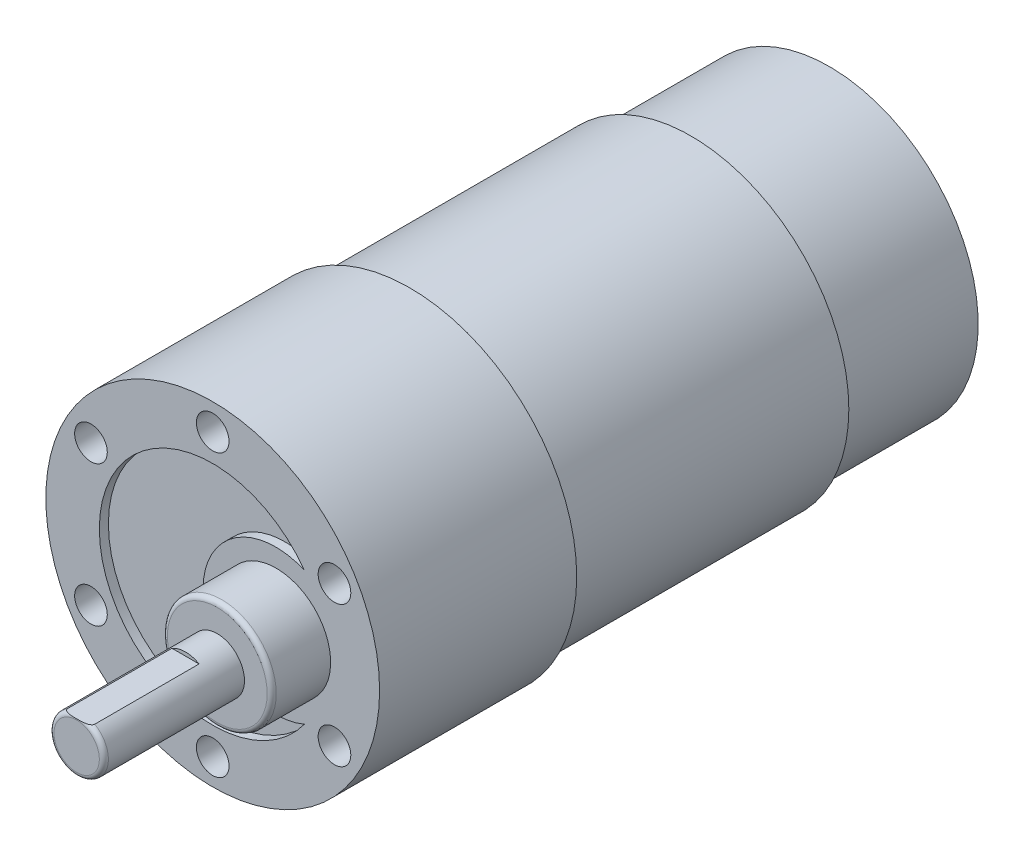
SolidWorks part; units mm, degrees
ref_plane "Front Plane" through (0, 0, 0) normal (0, 0, 1) x (1, 0, 0)
ref_plane "Top Plane" through (0, 0, 0) normal (0, 1, 0) x (1, 0, 0)
ref_plane "Right Plane" through (0, 0, 0) normal (1, 0, 0) x (0, 0, -1)
sketch "Sketch1" plane through (0, 0, 0) normal (0, 0, 1) x (1, 0, 0)
  circle A0 centre (0, 0) radius 18.4
  dimension "D1" = 36.8
extrude "Boss-Extrude1" add sketch "Sketch1" along normal blind 21.73
sketch "Sketch2" plane through (0, 0, 0) normal (0, 0, -1) x (-1, 0, 0)
  circle A0 centre (0, 0) radius 17.4
  dimension "D1" = 34.8
extrude "Boss-Extrude2" add sketch "Sketch2" along normal blind 31
sketch "Sketch3" plane through (0, 0, 21.73) normal (0, 0, 1) x (1, 0, 0)
  circle A0 centre (7, 0) radius 6
  dimension "D1" = 12
  dimension "D2" = 7
extrude "Boss-Extrude3" add sketch "Sketch3" along normal blind 6.5
fillet "Fillet1" radius 0.5 1 edges at (13, 0, 28.23)
sketch "Sketch4" plane through (0, 0, 28.23) normal (0, 0, 1) x (1, 0, 0)
  line L0 (7, -6.8172) -> (7, 7.1125) construction
  circle A0 centre (7, 0) radius 3
  dimension "D1" = 6
extrude "Boss-Extrude4" add sketch "Sketch4" along normal blind 15.5
sketch "Sketch5" plane through (0, 0, 43.73) normal (0, 0, 1) x (1, 0, 0)
  line L0 (5.5033, 2.6) -> (8.4967, 2.6)
  line L1 (7, -3) -> (9.3109, -3) construction
  circle A0 centre (7, 0) radius 3 construction
  circle A1 centre (7, 0) radius 3 construction
  arc A2 (8.4967, 2.6) -> (5.5033, 2.6) centre (7, 0) ccw
  dimension "D1" = 5.6
extrude "Cut-Extrude1" cut sketch "Sketch5" against normal blind 12
sketch "Sketch8" plane through (0, 0, 21.73) normal (0, 0, 1) x (1, 0, 0)
  line L0 (-0.5907, 0) -> (14.4711, 0) construction
  line L1 (7, 7.3586) -> (7, -7.457) construction
  arc A0 (10.1162, 7.3426) -> (10.1162, -7.3426) centre (0, 0) ccw
  arc A1 (10.1162, 7.3426) -> (10.1162, -7.3426) centre (6.9402, 0) ccw
  dimension "D1" = 25
  dimension "D2" = 16
extrude "Cut-Extrude2" cut sketch "Sketch8" against normal blind 1
sketch "Sketch9" plane through (0, 0, -31) normal (0, 0, -1) x (-1, 0, 0)
  circle A0 centre (0, 0) radius 4
  dimension "D1" = 8
extrude "Boss-Extrude5" add sketch "Sketch9" along normal blind 1
fillet "Fillet2" radius 0.5 1 edges at (-4, 0, -32)
ref_plane "Plane1" through (0, 0, -34) normal (0, 0, -1) x (-1, 0, 0)
sketch "Sketch10" plane through (0, 0, -34) normal (0, 0, -1) x (-1, 0, 0)
  circle A0 centre (0, 0) radius 14
  dimension "D1" = 28
extrude "Boss-Extrude6" add sketch "Sketch10" along normal blind 1.5 separate body
sketch "Sketch11" plane through (0, 0, -31) normal (0, 0, -1) x (-1, 0, 0)
  line L0 (0, 11.55) -> (0, 12.55) construction
  line L1 (-1.75, 12.55) -> (1.75, 12.55)
  line L2 (-1.75, 12.55) -> (-1.75, 11.55)
  line L3 (-1.75, 11.55) -> (1.75, 11.55)
  line L4 (1.75, 12.55) -> (1.75, 11.55)
  line L5 (-1.75, 12.05) -> (1.75, 12.05) construction
  line L6 (-3.5, 0) -> (3.5, 0) construction
  line L7 (1.75, -12.55) -> (1.75, -11.55)
  line L8 (-1.75, -12.55) -> (-1.75, -11.55)
  line L9 (-1.75, -12.55) -> (1.75, -12.55)
  line L10 (-1.75, -11.55) -> (1.75, -11.55)
  circle A0 centre (0, 0) radius 3.5 construction
  dimension "D1" = 3.5
  dimension "D2" = 1
  dimension "D3" = 12.05
extrude "Boss-Extrude7" add sketch "Sketch11" along normal blind 5.6
fillet "Fillet3" radius 0.5 4 edges at (-1.75, -12.05, -36.6) (1.75, -12.05, -36.6) (-1.75, 12.05, -36.6) (1.75, 12.05, -36.6)
ref_plane "Plane2" through (0, 0, -37.5) normal (0, 0, -1) x (-1, 0, 0)
sketch "Sketch13" plane through (0, 0, -37.5) normal (0, 0, -1) x (-1, 0, 0)
  circle A0 centre (0, 0) radius 9
  dimension "D1" = 18
extrude "Boss-Extrude8" add sketch "Sketch13" along normal blind 3 separate body
sketch "Sketch14" plane through (0, 0, -32) normal (0, 0, -1) x (-1, 0, 0)
  circle A0 centre (0, 0) radius 1.5
  dimension "D1" = 3
extrude "Boss-Extrude9" add sketch "Sketch14" along normal blind 8.55
fillet "Fillet4" radius 0.5 1 edges at (7, -3, 43.73)
sketch "Sketch15" plane through (0, 0, -31) normal (0, 0, -1) x (-1, 0, 0)
  circle A0 centre (0, 0) radius 16.4
  circle A1 centre (0, 0) radius 17.4 construction
  dimension "D1" = 1
extrude "Boss-Extrude10" add sketch "Sketch15" along normal blind 15.26
sketch "Sketch17" plane through (0, 0, 21.73) normal (0, 0, 1) x (1, 0, 0)
  line L0 (0, 0) -> (0, -15.5) construction
  circle A0 centre (0, 0) radius 15.5 construction
  circle A1 centre (0, -15.5) radius 1.8
  circle A2 centre (-13.4234, -7.75) radius 1.8
  circle A3 centre (-13.4234, 7.75) radius 1.8
  circle A4 centre (0, 15.5) radius 1.8
  circle A5 centre (13.4234, 7.75) radius 1.8
  circle A6 centre (13.4234, -7.75) radius 1.8
  point P18 (0, 0)
  dimension "D1" = 31
  dimension "D2" = 3.6
  dimension "D3" = 6
extrude "Cut-Extrude3" cut sketch "Sketch17" against normal blind 3
